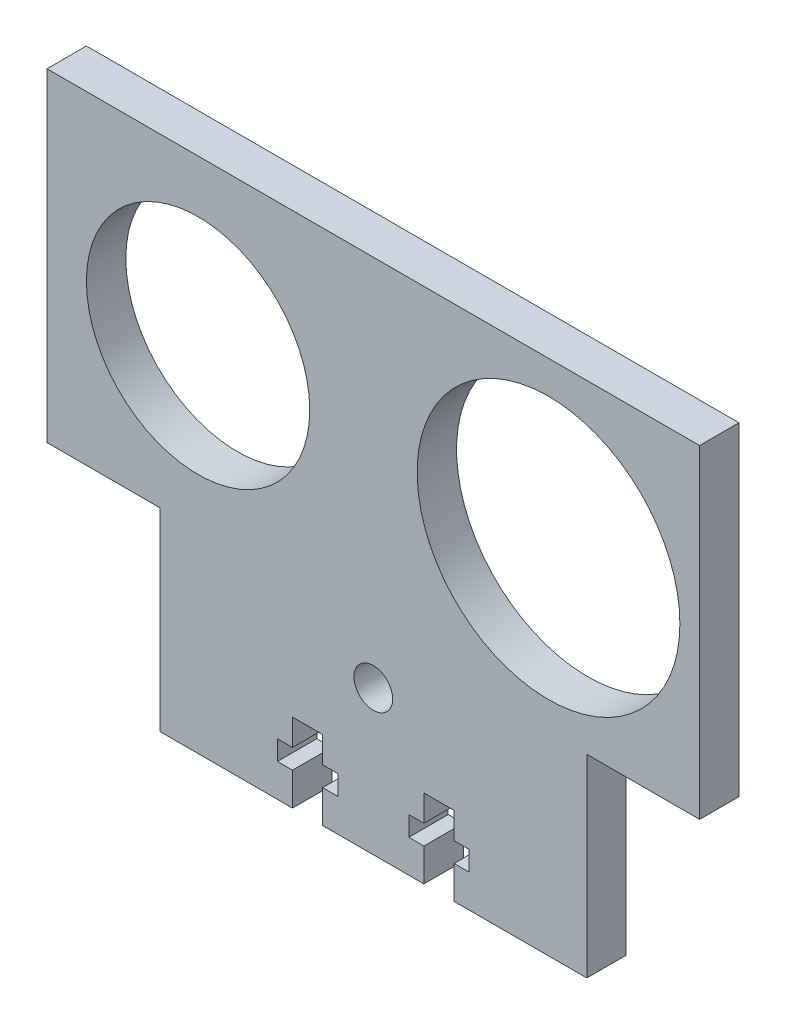
SolidWorks part; units mm, degrees
material "ABS"
ref_plane "Front Plane" through (0, 0, 0) normal (0, 0, 1) x (1, 0, 0)
ref_plane "Top Plane" through (0, 0, 0) normal (0, 1, 0) x (1, 0, 0)
ref_plane "Right Plane" through (0, 0, 0) normal (1, 0, 0) x (0, 0, -1)
sketch "Sketch1" plane through (0, 0, 0) normal (0, 0, 1) x (1, 0, 0)
  line L0 (0, 0) -> (-26.6757, 31.7908) construction
  line L1 (0, 0) -> (0, 56.7908) construction
  line L2 (-32.5, 7.5) -> (-32.5, -22)
  line L3 (-32.5, -22) -> (32.5, -22)
  line L4 (32.5, 7.5) -> (49.6757, 7.5)
  line L5 (0, 0) -> (0, -22) construction
  line L6 (49.6757, 7.5) -> (49.6757, 56.7908)
  line L7 (0, 0) -> (26.6757, 31.7908) construction
  line L10 (-32.5, 7.5) -> (-49.6757, 7.5)
  line L11 (-49.6757, 7.5) -> (-49.6757, 56.7908)
  line L12 (-49.6757, 56.7908) -> (49.6757, 56.7908)
  line L13 (32.5, 7.5) -> (32.5, -22)
  circle A0 centre (0, 0) radius 2.95
  circle A1 centre (-26.6757, 31.7908) radius 17
  circle A2 centre (26.6757, 31.7908) radius 20
  point P16 (0, 56.7908)
  dimension "D1" = 5.9
  dimension "D9" = 34
  dimension "D10" = 40
  dimension "D2" = 41.5
  dimension "D4" = 40
  dimension "D5" = 22
  dimension "D6" = 65
  dimension "D7" = 29.5
  dimension "D8" = 23
  dimension "D3" = 25
  dimension "D11" = 40
extrude "Boss-Extrude1" add sketch "Sketch1" along normal blind 6
sketch "Sketch3" plane through (0, 0, 6) normal (0, 0, 1) x (1, 0, 0)
  line L0 (-32.5, -22) -> (32.5, -22) construction
  line L1 (-12.3, -22) -> (-7.7, -22)
  line L2 (-12.3, -22) -> (-12.3, -17)
  line L3 (-12.3, -10) -> (-7.7, -10)
  line L4 (-7.7, -22) -> (-7.7, -17)
  line L5 (0, 0) -> (0, -22) construction
  line L6 (-7.7, -14) -> (-5.4, -14)
  line L7 (-14.6, -14) -> (-12.3, -14)
  line L8 (-14.6, -14) -> (-14.6, -17)
  line L9 (-14.6, -17) -> (-12.3, -17)
  line L10 (-5.4, -14) -> (-5.4, -17)
  line L11 (-12.3, -14) -> (-12.3, -10)
  line L12 (-7.7, -17) -> (-5.4, -17)
  line L13 (-7.7, -14) -> (-7.7, -10)
  line L14 (7.7, -14) -> (7.7, -10)
  line L15 (7.7, -17) -> (5.4, -17)
  line L16 (12.3, -14) -> (12.3, -10)
  line L17 (5.4, -14) -> (5.4, -17)
  line L18 (14.6, -17) -> (12.3, -17)
  line L19 (14.6, -14) -> (14.6, -17)
  line L20 (14.6, -14) -> (12.3, -14)
  line L21 (7.7, -14) -> (5.4, -14)
  line L22 (7.7, -22) -> (7.7, -17)
  line L23 (12.3, -10) -> (7.7, -10)
  line L24 (12.3, -22) -> (12.3, -17)
  line L25 (12.3, -22) -> (7.7, -22)
  point P6 (-10, -10)
  point P18 (-13.45, -17)
  dimension "D1" = 4.6
  dimension "D2" = 10
  dimension "D3" = 12
  dimension "D4" = 9.2
  dimension "D5" = 3
  dimension "D6" = 5
extrude "Cut-Extrude2" cut sketch "Sketch3" against normal through all
equation "\"smallPulleyTeeth\"= 30"
equation "\"largePulleyTeeth\"= 30"
equation "\"eighthThick\"= 3.0mm"
equation "\"sixteenthThick\"= 1.7mm"
equation "\"quarterThick\"=6.0mm"
equation "\"OD\"= 145mm"
equation "\"puckAngle\"= 60.5deg"
equation "\"puckDiam\"= 76.5mm"
equation "\"axlePress\"= 5.9mm"
equation "\"D1@Sketch1\"=\"axlePress\""
equation "\"D1@Boss-Extrude1\"=\"quarterThick\""
equation "\"press\"= 0.2mm"
equation "\"wheelClear\"= 0.3mm"
equation "\"10-32clear\"= 4.8mm"
equation "\"D1@Sketch3\"=\"10-32clear\" - \"press\""
equation "\"6-32clear\"= 3.3mm"
equation "\"8-32clear\"= 4.0mm"
equation "\"wheelHeight\"= 22mm"
equation "\"D5@Sketch1\"=\"wheelHeight\""
equation "\"4-40clear\"= 3.0mm"
equation "\"wheelWell\"= 65mm"
equation "\"D6@Sketch1\"=\"wheelWell\""
equation "\"D7@Sketch1\"=\"eighthThick\"*10 - 0.5"
